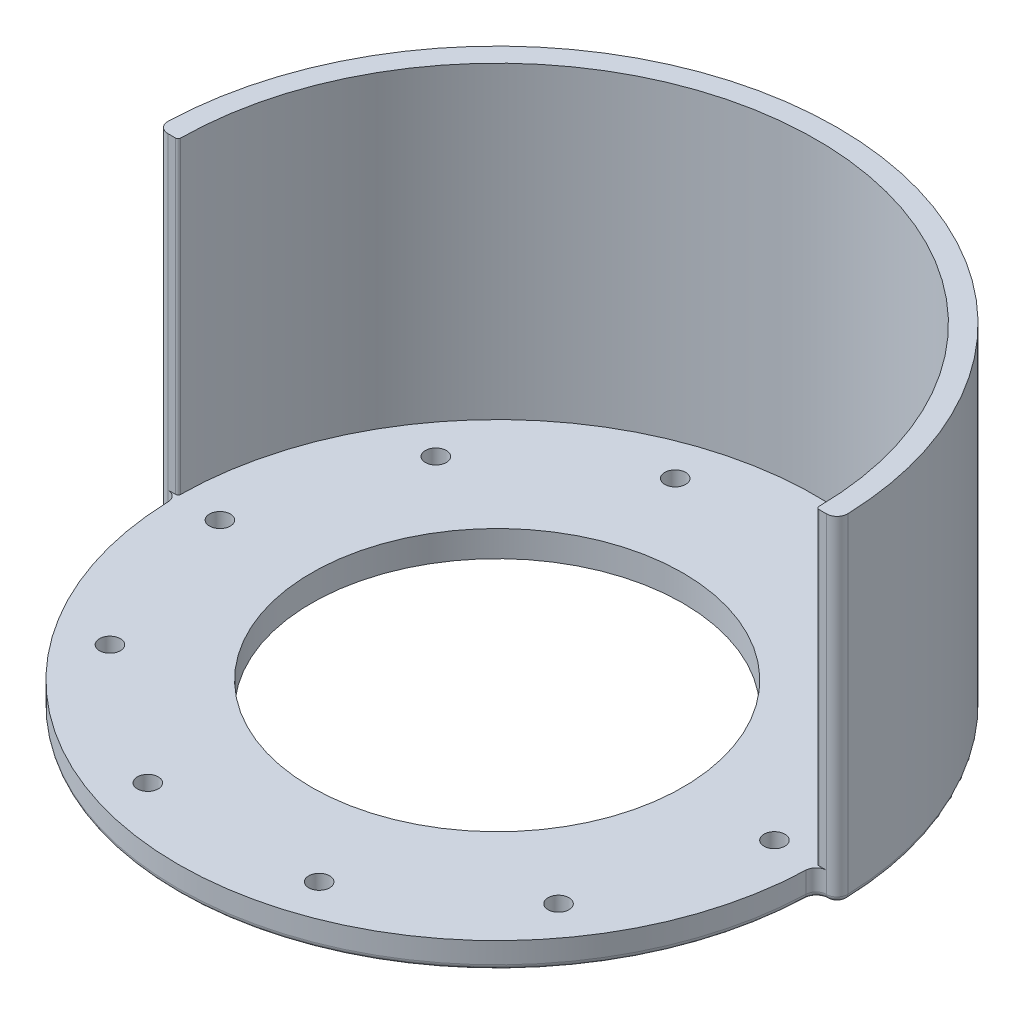
SolidWorks part; units mm, degrees
ref_plane "Спереди" through (0, 0, 0) normal (0, 0, 1) x (1, 0, 0)
ref_plane "Сверху" through (0, 0, 0) normal (0, 1, 0) x (1, 0, 0)
ref_plane "Справа" through (0, 0, 0) normal (1, 0, 0) x (0, 0, -1)
sketch "Эскиз3" plane through (0, 0, 0) normal (0, 1, 0) x (1, 0, 0)
  line L0 (-61, 0) -> (-65, 0)
  line L1 (65, 0) -> (61, 0)
  circle A2 centre (0, 0) radius 61
  arc A3 (65, 0) -> (-65, 0) centre (0, 0) ccw
  dimension "D1" = 130
  dimension "D2" = 122
extrude "Бобышка-Вытянуть2" add sketch "Эскиз3" along normal blind 5 contours A2 region at (0, 0, 0)
extrude "Бобышка-Вытянуть3" add sketch "Эскиз3<5>" along normal blind 64 contours A2 region at (-63, 0, -1.4534)
sketch "Эскиз3<5>" plane through (0, 0, 0) normal (0, 1, 0) x (1, 0, 0) same geometry as "Эскиз3"
sketch "Эскиз4" plane through (0, 5, 0) normal (0, 1, 0) x (1, 0, 0)
  line L0 (0, 0) -> (-53, 0) construction
  circle A0 centre (0, 0) radius 53
  circle A1 centre (0, 0) radius 35.5
  circle A2 centre (-53, 0) radius 2
  circle A3 centre (0, 0) radius 53
  circle A4 centre (-42.8779, 31.1526) radius 2
  circle A5 centre (0, 0) radius 53
  circle A6 centre (-16.3779, 50.406) radius 2
  circle A7 centre (0, 0) radius 53
  circle A8 centre (16.3779, 50.406) radius 2
  circle A9 centre (0, 0) radius 53
  circle A10 centre (42.8779, 31.1526) radius 2
  circle A11 centre (0, 0) radius 53
  circle A12 centre (53, 0) radius 2
  circle A13 centre (0, 0) radius 53
  circle A14 centre (42.8779, -31.1526) radius 2
  circle A15 centre (0, 0) radius 53
  circle A16 centre (16.3779, -50.406) radius 2
  circle A17 centre (0, 0) radius 53
  circle A18 centre (-16.3779, -50.406) radius 2
  circle A19 centre (0, 0) radius 53
  circle A20 centre (-42.8779, -31.1526) radius 2
  dimension "D1" = 106
  dimension "D2" = 71
  dimension "D3" = 4
  dimension "D4" = 10
extrude "Вырез-Вытянуть2" cut sketch "Эскиз4" against normal blind 5 contours A1 | A4 | A6 | A8 | A10 | A12 | A14 | A16 | A18 | A20 | A2 region at (0, 5, 0)
ref_plane "Плоскость муфты" through (0, 0, -66) normal (0, 0, -1) x (-1, 0, 0)
fillet "Скругление10" radius 2 2 edges at (-61, 2.5, 0) (61, 2.5, 0)
fillet "Скругление11" radius 0.5 2 edges at (61, 34.5, 0) (-61, 34.5, 0)
fillet "Скругление12" radius 2 2 edges at (65, 32, 0) (-65, 32, 0)
fillet "Скругление13" radius 1 6 edges at (64.4047, 0, -0.6084) (61.5767, 0, 0.5635) (0, 0, 61) (-61.5767, 0, 0.5635) (-64.4047, 0, -0.6084) (0, 0, -65)
